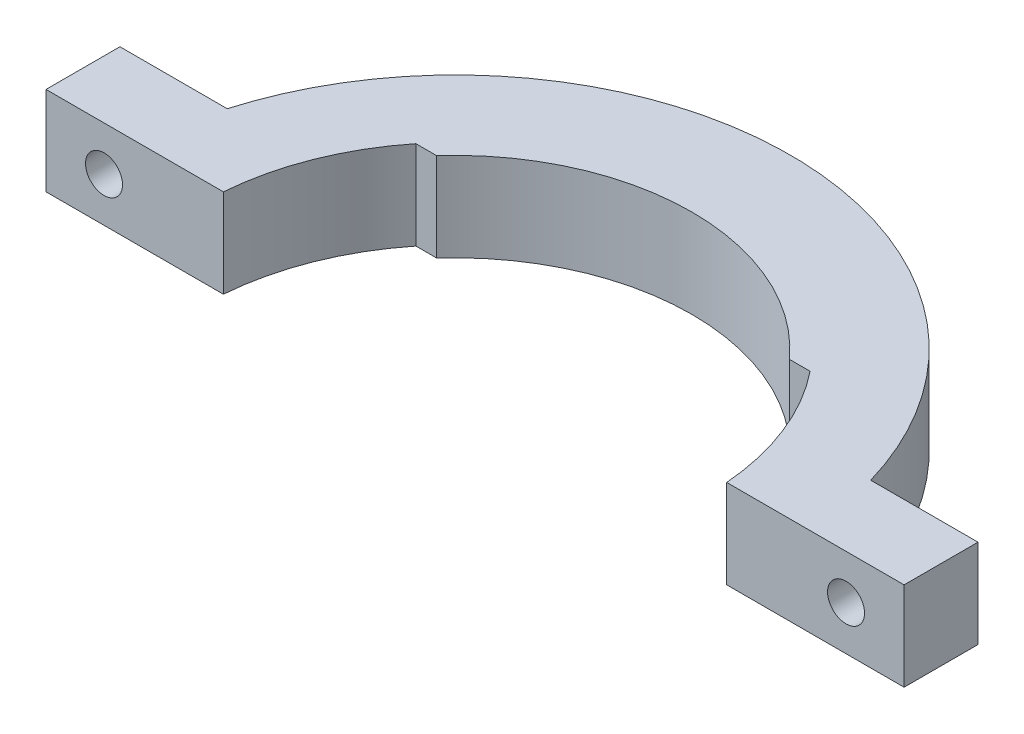
SolidWorks part; units mm, degrees
ref_plane "Alzado" through (0, 0, 0) normal (0, 0, 1) x (1, 0, 0)
ref_plane "Planta" through (0, 0, 0) normal (0, 1, 0) x (1, 0, 0)
ref_plane "Vista lateral" through (0, 0, 0) normal (1, 0, 0) x (0, 0, -1)
sketch "Croquis1" plane through (0, 0, 0) normal (0, 1, 0) x (1, 0, 0)
  line L0 (0, 0) -> (49.0196, 0) construction
  line L1 (0, 0) -> (0, 37.1025) construction
  line L2 (17.8885, 16) -> (20, 16)
  line L3 (25.5343, 2) -> (43.5343, 2)
  line L4 (43.5343, 2) -> (43.5343, 9.5)
  line L5 (43.5343, 9.5) -> (32.6458, 9.5)
  line L6 (-43.5343, 2) -> (-43.5343, 9.5)
  line L7 (-43.5343, 9.5) -> (-32.6458, 9.5)
  line L8 (-25.5343, 2) -> (-43.5343, 2)
  line L9 (-17.8885, 16) -> (-20, 16)
  arc A0 (17.8885, 16) -> (-17.8885, 16) centre (0, 0) ccw
  arc A1 (25.5343, 2) -> (20, 16) centre (0, 0) ccw
  arc A2 (32.6458, 9.5) -> (-32.6458, 9.5) centre (0, 0) ccw
  arc A3 (-25.5343, 2) -> (-20, 16) centre (0, 0) cw
  dimension "D1" = 24
  dimension "D2" = 25.6125
  dimension "D3" = 34
  dimension "D8" = 24
  dimension "D4" = 16
  dimension "D5" = 2
  dimension "D6" = 18
  dimension "D7" = 7.5
  dimension "D10" = 2.1115
extrude "Saliente-Extruir1" add sketch "Croquis1" along normal blind 9
sketch "Croquis2" plane through (0, 0, -9.5) normal (0, 0, -1) x (-1, 0, 0)
  line L1 (-32.6458, 9) -> (-32.6458, 0) construction
  line L2 (0, 0) -> (0, 9) construction
  line L3 (-32.6458, 0) -> (32.6458, 0) construction
  line L4 (32.6458, 9) -> (-32.6458, 9) construction
  circle A0 centre (-37.645, 4.5) radius 3.5
  circle A1 centre (-37.645, 4.5) radius 1.875
  circle A2 centre (37.645, 4.5) radius 1.875
  circle A3 centre (37.645, 4.5) radius 3.5
  point P10 (-32.6458, 4.5)
  dimension "D1" = 3.75
  dimension "D2" = 7
  dimension "D3" = 37.645
extrude "Cortar-Extruir1" cut sketch "Croquis2" against normal through all contours A2 | A1 region at (-37.645, 4.5, -9.5)
extrude "Cortar-Extruir2" cut sketch "Croquis2<3>" against normal blind 2.8
sketch "Croquis2<3>" plane through (0, 0, -9.5) normal (0, 0, -1) x (-1, 0, 0) same geometry as "Croquis2"
